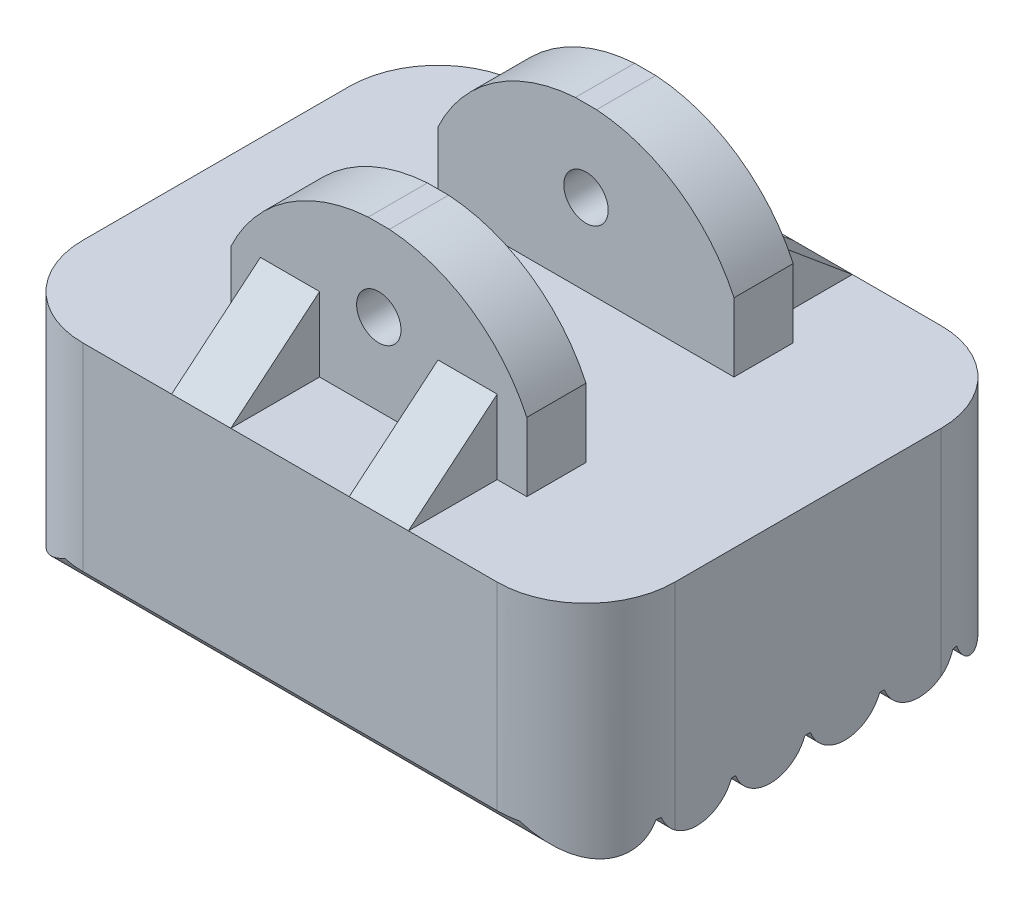
SolidWorks part; units mm, degrees
ref_plane "Front Plane" through (0, 0, 0) normal (0, 0, 1) x (1, 0, 0)
ref_plane "Top Plane" through (0, 0, 0) normal (0, 1, 0) x (1, 0, 0)
ref_plane "Right Plane" through (0, 0, 0) normal (1, 0, 0) x (0, 0, -1)
sketch "Sketch1" plane through (0, 0, 0) normal (0, 1, 0) x (1, 0, 0)
  line L1 (0, 0) -> (40, 0)
  line L2 (0, 0) -> (0, 30)
  line L3 (0, 30) -> (40, 30)
  line L4 (40, 0) -> (40, 30)
  dimension "D1" = 40
  dimension "D2" = 30
extrude "Boss-Extrude1" add sketch "Sketch1" along normal blind 15
sketch "Sketch2" plane through (0, 15, 0) normal (0, 1, 0) x (1, 0, 0)
  line L0 (0, 15) -> (40, 15) construction
  line L1 (10, 24) -> (30, 24)
  line L2 (10, 24) -> (10, 20)
  line L3 (10, 20) -> (30, 20)
  line L4 (30, 24) -> (30, 20)
  line L5 (10, 10) -> (30, 10)
  line L6 (10, 10) -> (10, 6)
  line L7 (10, 6) -> (30, 6)
  line L8 (30, 10) -> (30, 6)
  line L9 (0, 30) -> (0, 0) construction
  line L10 (40, 0) -> (40, 30) construction
  line L11 (20, 30) -> (20, 0) construction
  line L12 (40, 30) -> (0, 30) construction
  line L13 (0, 0) -> (40, 0) construction
  dimension "D1" = 10
  dimension "D2" = 5
  dimension "D3" = 4
  dimension "D4" = 4
  dimension "D5" = 10
  dimension "D6" = 10
  dimension "D7" = 10
  dimension "D8" = 10
extrude "Boss-Extrude2" add sketch "Sketch2" along normal blind 11
sketch "Sketch3" plane through (0, 0, -6) normal (0, 0, 1) x (1, 0, 0)
  line L0 (20, 26) -> (20, 15) construction
  line L1 (10, 26) -> (30, 26) construction
  line L2 (10, 15) -> (30, 15) construction
  line L3 (10, 20.5) -> (30, 20.5) construction
  line L4 (10, 26) -> (10, 15) construction
  line L5 (30, 26) -> (30, 15) construction
  line L6 (20, 22) -> (20, 26) construction
  line L7 (10, 19.6381) -> (10, 26)
  line L8 (10, 26) -> (30, 26)
  line L9 (30, 26) -> (30, 19.6381)
  circle A0 centre (20, 20.5) radius 1.5
  arc A1 (30, 19.6381) -> (10, 19.6381) centre (20, 15) ccw
  line M7 (30, 15) -> (30, 26)
  line M8 (30, 26) -> (10, 26)
  line M9 (10, 26) -> (10, 15)
  dimension "D1" = 3
extrude "Cut-Extrude1" cut sketch "Sketch3" against normal blind 20 contours A1 M8 M9 | A1 M7 M8 | A0 region at (27.6969, 24.2417, -6) region at (12.3031, 24.2417, -6) region at (20, 20.5, -6)
sketch "Sketch4" plane through (0, 15, 0) normal (0, 1, 0) x (1, 0, 0)
  line L0 (30, 24) -> (10, 24) construction
  line L1 (12, 24) -> (16, 24)
  line L2 (12, 24) -> (12, 30)
  line L3 (12, 30) -> (16, 30)
  line L4 (16, 24) -> (16, 30)
  line L5 (40, 30) -> (0, 30) construction
  line L6 (12, 24) -> (12, 0) construction
  line L7 (28, 30) -> (24, 30)
  line L8 (28, 30) -> (28, 24)
  line L9 (28, 24) -> (24, 24)
  line L10 (24, 30) -> (24, 24)
  line L11 (0, 0) -> (40, 0) construction
  line L12 (16, 24) -> (16, 0) construction
  line L13 (24, 24) -> (24, 0) construction
  line L14 (28, 24) -> (28, 0) construction
  line L15 (10, 6) -> (30, 6) construction
  line L16 (12, 6) -> (16, 6)
  line L17 (12, 6) -> (12, 0)
  line L18 (12, 0) -> (16, 0)
  line L19 (16, 6) -> (16, 0)
  line L21 (24, 6) -> (28, 6)
  line L22 (24, 6) -> (24, 0)
  line L23 (24, 0) -> (28, 0)
  line L24 (28, 6) -> (28, 0)
  dimension "D1" = 2
  dimension "D2" = 2
  dimension "D3" = 4
  dimension "D4" = 4
  dimension "D5" = 8
extrude "Boss-Extrude3" add sketch "Sketch4" along normal blind 5
sketch "Sketch5" plane through (28, 0, 0) normal (1, 0, 0) x (0, 0, -1)
  line L0 (0, 15) -> (0, 20)
  line L1 (0, 20) -> (6, 20)
  line L2 (6, 20) -> (0, 15)
  line L3 (24, 20) -> (30, 20)
  line L4 (30, 20) -> (30, 15)
  line L5 (30, 15) -> (24, 20)
extrude "Cut-Extrude2" cut sketch "Sketch5" against normal blind 21 contours L2 L0 L1 | L5 L3 L4
fillet "Fillet7" radius 6 1 edges at (0, 7.5, 0) type face fillet first side face at (0, 7.5, -15) second side face at (20, 11.25, 0)
fillet "Fillet8" radius 6 1 edges at (0, 7.5, -30) type face fillet first side face at (0, 7.5, -18) second side face at (20, 11.25, -30)
fillet "Fillet9" radius 6 1 edges at (40, 7.5, -30) type face fillet first side face at (40, 7.5, -15) second side face at (21.5, 11.25, -30)
fillet "Fillet10" radius 6 1 edges at (40, 7.5, 0) type face fillet first side face at (21.5, 11.25, 0) second side face at (40, 7.5, -12)
sketch "Sketch6" plane through (0, 0, 0) normal (-1, 0, 0) x (0, 0, 1)
  line L1 (-30, 2.5) -> (-30, 0)
  line L3 (-30, 0) -> (0, 0)
  line L6 (-30, 0) -> (-30, 2.5) construction
  line L7 (0, 0) -> (0, 2.5)
  line L8 (-30, 0) -> (-30, 15) construction
  line L9 (-30, 2.5) -> (0, 2.5) construction
  line L10 (-15, 2.5) -> (-14.9464, 2.5)
  line L11 (0, 15) -> (0, 0) construction
  line L12 (-30, 1.6244) -> (0, 1.6244)
  arc A0 (-30, 2.5) -> (-25, 2.5) centre (-27.5, 2.5) ccw
  arc A2 (-20, 2.5) -> (-15, 2.5) centre (-17.5, 2.5) ccw
  arc A3 (-25, 2.5) -> (-20, 2.5) centre (-22.5, 2.5) ccw
  arc A4 (-14.9464, 2.5) -> (-9.9686, 2.8323) centre (-12.4464, 2.5) ccw
  arc A5 (-9.9686, 2.8323) -> (-4.9931, 2.6069) centre (-7.4908, 2.5) ccw
  arc A6 (-4.9931, 2.6069) -> (0, 2.3483) centre (-2.4954, 2.5) ccw
  line M6 (-24, 15) -> (-24, 0)
  line M7 (-24, 0) -> (-6, 0)
  line M8 (-6, 0) -> (-6, 15)
  dimension "D2" = 5
  dimension "D3" = 5
  dimension "D4" = 5
  dimension "D5" = 5
  dimension "D6" = 5
  dimension "D7" = 5
  dimension "D1" = 2.5
extrude "Cut-Extrude5" cut sketch "Sketch6" against normal blind 44 contours A0 L1 L3 | A3 A0 L3 M6 | A3 M6 M7 | A3 L3 A2 | A4 L10 A2 L3 | A5 A4 M7 | A6 A5 L3 M8 | A6 L3 L7 | A5 L3 M8 region at (0, 0.5132, -29.4236) region at (0, 0.5504, -25.1389) region at (0, 0.147, -23.6329) region at (0, 0.5132, -20) region at (0, 0.5229, -14.9732) region at (0, 0.5047, -9.9686) region at (0, 0.1451, -6.365) region at (0, 0.549, -4.8562) region at (0, 0.5115, -0.5751)
